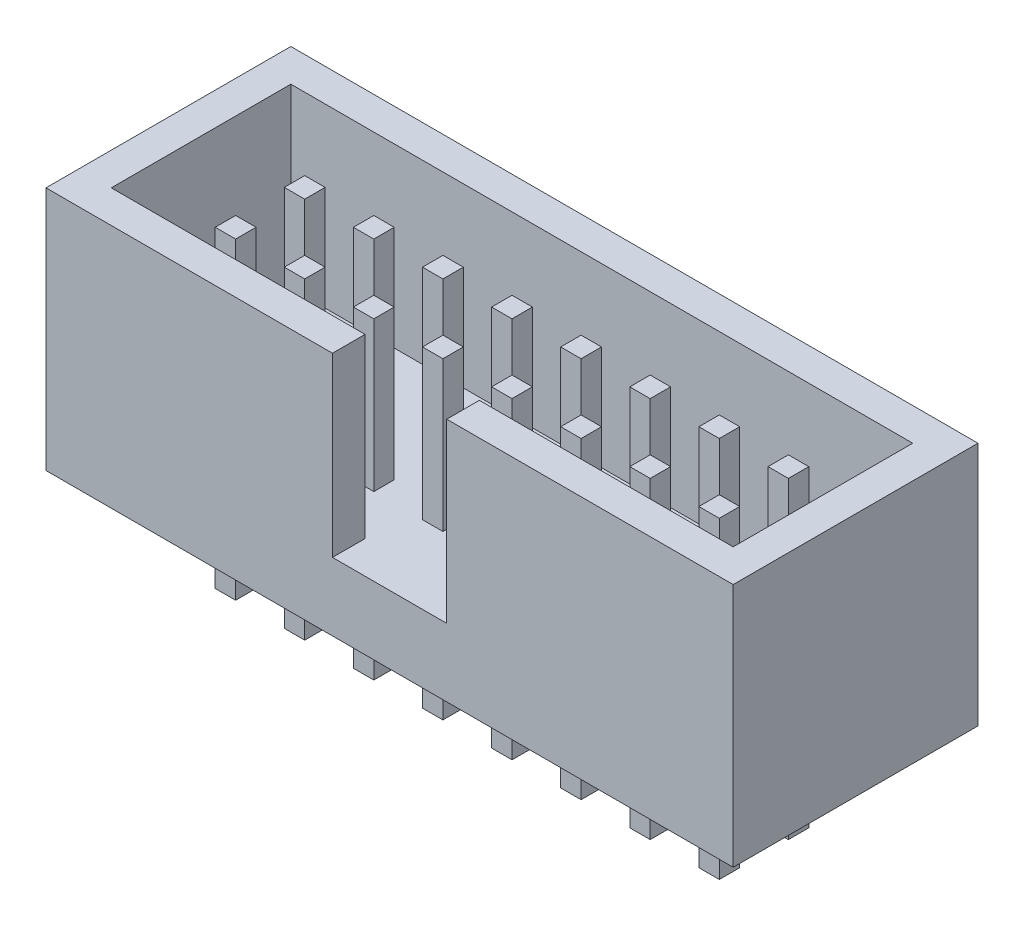
SolidWorks part; units mm, degrees
ref_plane "前视基准面" through (0, 0, 0) normal (0, 0, 1) x (1, 0, 0)
ref_plane "上视基准面" through (0, 0, 0) normal (0, 1, 0) x (1, 0, 0)
ref_plane "右视基准面" through (0, 0, 0) normal (1, 0, 0) x (0, 0, -1)
sketch "草图1" plane through (0, 0, 0) normal (0, 1, 0) x (1, 0, 0)
  line L0 (0, 85.0964) -> (0, -118.2031) construction
  line L1 (-12.63, 4.5) -> (12.63, 4.5)
  line L2 (-12.63, 4.5) -> (-12.63, -4.5)
  line L3 (-12.63, -4.5) -> (12.63, -4.5)
  line L4 (12.63, 4.5) -> (12.63, -4.5)
  line L5 (-200.5452, 0) -> (261.2352, 0) construction
  dimension "D1" = 9
  dimension "D2" = 25.26
extrude "拉伸1" add sketch "草图1" along normal blind 9
sketch "草图2" plane through (0, 9, 0) normal (0, 1, 0) x (-1, 0, 0)
  line L8 (-11.43, 3.3) -> (-11.43, -3.3)
  line L9 (11.43, 3.3) -> (-11.43, 3.3)
  line L10 (11.43, -3.3) -> (11.43, 3.3)
  line L11 (-11.43, -3.3) -> (11.43, -3.3)
  line L12 (-11.43, 3.3) -> (-11.43, -3.3)
  line L13 (11.43, 3.3) -> (-11.43, 3.3)
  line L14 (11.43, -3.3) -> (11.43, 3.3)
  line L15 (-11.43, -3.3) -> (11.43, -3.3)
  dimension "D1" = 1.2
extrude "切除-拉伸1" cut sketch "草图2" against normal blind 6.5
sketch "草图3" plane through (0, 0, 4.5) normal (0, 0, 1) x (1, 0, 0)
  line L0 (-12.63, 9) -> (12.63, 9) construction
  line L1 (-2.1, 9) -> (2.1, 9)
  line L2 (-2.1, 9) -> (-2.1, 2.5)
  line L3 (-2.1, 2.5) -> (2.1, 2.5)
  line L4 (2.1, 9) -> (2.1, 2.5)
  line L5 (-11.43, 2.5) -> (11.43, 2.5) construction
  line L6 (0, 9.4226) -> (0, -4.0288) construction
  dimension "D1" = 4.2
extrude "切除-拉伸2" cut sketch "草图3" against normal blind 6.5
sketch "草图5" plane through (0, 0, 0) normal (0, -1, 0) x (1, 0, 0)
  line L0 (0, 6.0683) -> (0, -6.9786) construction
  line L1 (-14.7999, 0) -> (15.2382, 0) construction
  line L2 (-1.27, 2.5244) -> (-1.27, -0.4442) construction
  line L3 (-1.645, 0.895) -> (-0.895, 0.895)
  line L4 (-1.645, 0.895) -> (-1.645, 1.645)
  line L5 (-1.645, 1.645) -> (-0.895, 1.645)
  line L6 (-0.895, 0.895) -> (-0.895, 1.645)
  line L7 (-2.3518, 1.27) -> (0.5396, 1.27) construction
  line L8 (-4.185, 0.895) -> (-3.435, 0.895)
  line L9 (-4.185, 0.895) -> (-4.185, 1.645)
  line L10 (-4.185, 1.645) -> (-3.435, 1.645)
  line L11 (-3.435, 0.895) -> (-3.435, 1.645)
  line L12 (-6.725, 0.895) -> (-5.975, 0.895)
  line L13 (-6.725, 0.895) -> (-6.725, 1.645)
  line L14 (-6.725, 1.645) -> (-5.975, 1.645)
  line L15 (-5.975, 0.895) -> (-5.975, 1.645)
  line L16 (-9.265, 0.895) -> (-8.515, 0.895)
  line L17 (-9.265, 0.895) -> (-9.265, 1.645)
  line L18 (-9.265, 1.645) -> (-8.515, 1.645)
  line L19 (-8.515, 0.895) -> (-8.515, 1.645)
  line L20 (-8.515, -0.895) -> (-8.515, -1.645)
  line L21 (-9.265, -1.645) -> (-8.515, -1.645)
  line L22 (-9.265, -0.895) -> (-9.265, -1.645)
  line L23 (-9.265, -0.895) -> (-8.515, -0.895)
  line L24 (-5.975, -0.895) -> (-5.975, -1.645)
  line L25 (-6.725, -1.645) -> (-5.975, -1.645)
  line L26 (-6.725, -0.895) -> (-6.725, -1.645)
  line L27 (-6.725, -0.895) -> (-5.975, -0.895)
  line L28 (-3.435, -0.895) -> (-3.435, -1.645)
  line L29 (-4.185, -1.645) -> (-3.435, -1.645)
  line L30 (-4.185, -0.895) -> (-4.185, -1.645)
  line L31 (-4.185, -0.895) -> (-3.435, -0.895)
  line L32 (-0.895, -0.895) -> (-0.895, -1.645)
  line L33 (-1.645, -1.645) -> (-0.895, -1.645)
  line L34 (-1.645, -0.895) -> (-1.645, -1.645)
  line L35 (-1.645, -0.895) -> (-0.895, -0.895)
  line L36 (1.27, 2.5244) -> (1.27, -0.4442) construction
  line L37 (1.645, -0.895) -> (0.895, -0.895)
  line L38 (1.645, -0.895) -> (1.645, -1.645)
  line L39 (1.645, -1.645) -> (0.895, -1.645)
  line L40 (0.895, -0.895) -> (0.895, -1.645)
  line L41 (4.185, -0.895) -> (3.435, -0.895)
  line L42 (4.185, -0.895) -> (4.185, -1.645)
  line L43 (4.185, -1.645) -> (3.435, -1.645)
  line L44 (3.435, -0.895) -> (3.435, -1.645)
  line L45 (6.725, -0.895) -> (5.975, -0.895)
  line L46 (6.725, -0.895) -> (6.725, -1.645)
  line L47 (6.725, -1.645) -> (5.975, -1.645)
  line L48 (5.975, -0.895) -> (5.975, -1.645)
  line L49 (9.265, -0.895) -> (8.515, -0.895)
  line L50 (9.265, -0.895) -> (9.265, -1.645)
  line L51 (9.265, -1.645) -> (8.515, -1.645)
  line L52 (8.515, -0.895) -> (8.515, -1.645)
  line L53 (8.515, 0.895) -> (8.515, 1.645)
  line L54 (9.265, 1.645) -> (8.515, 1.645)
  line L55 (9.265, 0.895) -> (9.265, 1.645)
  line L56 (9.265, 0.895) -> (8.515, 0.895)
  line L57 (5.975, 0.895) -> (5.975, 1.645)
  line L58 (6.725, 1.645) -> (5.975, 1.645)
  line L59 (6.725, 0.895) -> (6.725, 1.645)
  line L60 (6.725, 0.895) -> (5.975, 0.895)
  line L61 (3.435, 0.895) -> (3.435, 1.645)
  line L62 (4.185, 1.645) -> (3.435, 1.645)
  line L63 (4.185, 0.895) -> (4.185, 1.645)
  line L64 (4.185, 0.895) -> (3.435, 0.895)
  line L65 (0.895, 0.895) -> (0.895, 1.645)
  line L66 (1.645, 1.645) -> (0.895, 1.645)
  line L67 (1.645, 0.895) -> (1.645, 1.645)
  line L68 (1.645, 0.895) -> (0.895, 0.895)
  dimension "D1" = 0.75
  dimension "D2" = 0.75
  dimension "D3" = 1.27
  dimension "D4" = 1.27
extrude "拉伸2" add sketch "草图5" along normal blind 3.5 and the other way offset from surface 1 other way up to face at (0, 9, 1.3)
sketch "草图6" plane through (0, 0, 0) normal (0, -1, 0) x (1, 0, 0)
  line L0 (14.8773, 0) -> (-15.139, 0) construction
  line L1 (0, 6.7624) -> (0, -6.108) construction
  line L6 (-8.515, 1.645) -> (-9.265, 1.645) construction
  line L8 (-9.265, 1.645) -> (-9.265, 0.895) construction
  line L9 (-9.265, 0.895) -> (-8.515, 0.895) construction
  circle A0 centre (-8.89, 1.27) radius 0.375
